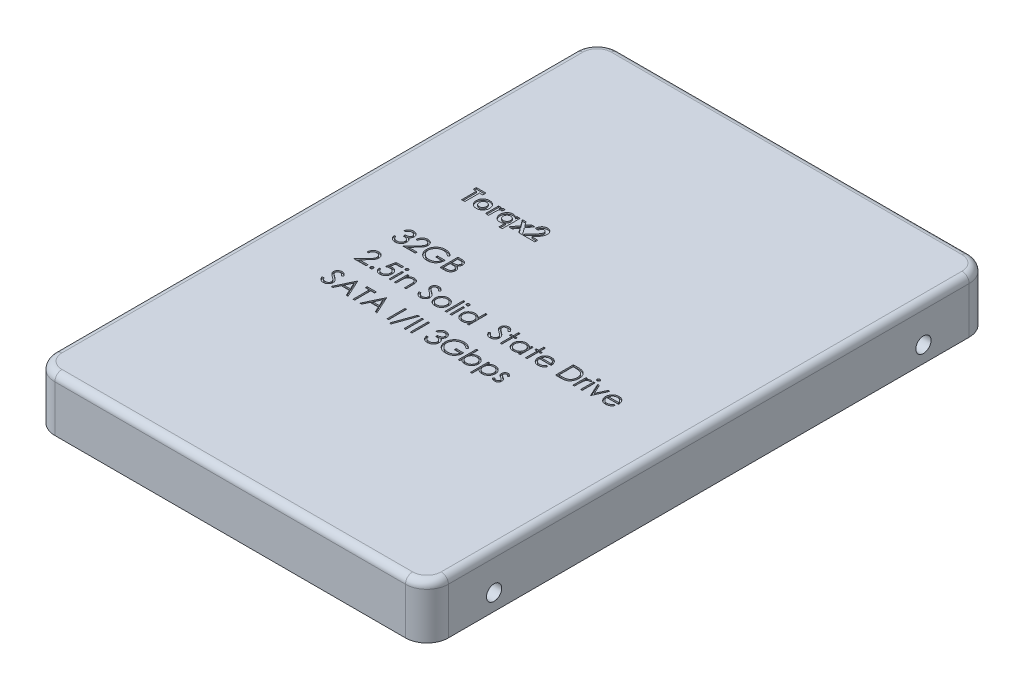
SolidWorks part; units mm, degrees
ref_plane "Front Plane" through (0, 0, 0) normal (0, 0, 1) x (1, 0, 0)
ref_plane "Top Plane" through (0, 0, 0) normal (0, 1, 0) x (1, 0, 0)
ref_plane "Right Plane" through (0, 0, 0) normal (1, 0, 0) x (0, 0, -1)
sketch "Sketch1" plane through (0, 0, 0) normal (0, 1, 0) x (1, 0, 0)
  line L1 (-34.925, -50.0253) -> (34.925, -50.0253)
  line L2 (-34.925, -50.0253) -> (-34.925, 50.0253)
  line L3 (-34.925, 50.0253) -> (34.925, 50.0253)
  line L4 (34.925, -50.0253) -> (34.925, 50.0253)
  line L5 (-34.925, -50.0253) -> (34.925, 50.0253) construction
  line L6 (-34.925, 50.0253) -> (34.925, -50.0253) construction
  point P0 (0, 0)
  dimension "D1" = 100.0506
  dimension "D2" = 69.85
extrude "Boss-Extrude1" add sketch "Sketch1" along normal mid plane 9.525
fillet "Fillet1" radius 3.81 4 edges at (-34.925, 0, -50.0253) (34.925, 0, -50.0253) (-34.925, 0, 50.0253) (34.925, 0, 50.0253)
fillet "Fillet2" radius 1.27 8 edges at (-33.8091, 4.7625, -48.9094) (0, 4.7625, -50.0253) (33.8091, 4.7625, -48.9094) (34.925, 4.7625, 0) (33.8091, 4.7625, 48.9094) (0, 4.7625, 50.0253) (-33.8091, 4.7625, 48.9094) (-34.925, 4.7625, 0)
hole_wizard "#6-32 Tapped Hole1" positions "Sketch3" profile "Sketch2" tap size "#6-32" standard "Ansi Inch"
sketch "Sketch3" plane through (0, -4.7625, 0) normal (0, -1, 0) x (1, 0, 0)
  line L1 (-30.7975, -38.1) -> (30.7975, -38.1) construction
  line L2 (-30.7975, -38.1) -> (-30.7975, 38.1) construction
  line L3 (-30.7975, 38.1) -> (30.7975, 38.1) construction
  line L4 (30.7975, -38.1) -> (30.7975, 38.1) construction
  line L5 (-30.7975, -38.1) -> (30.7975, 38.1) construction
  line L6 (-30.7975, 38.1) -> (30.7975, -38.1) construction
  point P0 (-30.7975, -38.1)
  point P212 (0, 0)
  point P214 (-30.7975, 38.1)
  point P216 (30.7975, 38.1)
  point P218 (30.7975, -38.1)
  dimension "D1" = 76.2
  dimension "D2" = 61.595
sketch "Sketch2" plane through (-30.7975, -4.7625, -38.1) normal (1, 0, 0) x (0, 0, -1)
  line L0 (0, 0) -> (0, 5.8927)
  line L1 (0, 5.8927) -> (1.3525, 5.08)
  line L2 (1.3525, 5.08) -> (1.3525, 0)
  line L5 (1.3525, 0) -> (0, 0)
  line L10 (0, 5.8927) -> (-1.3526, 5.08) construction
  line L11 (0, -6.35) -> (0, 107.95) construction
  dimension "Tap Drill Dia." = 2.7051
  dimension "Tap Drill Depth" = 5.08
  dimension "Drill Angle" = 118
hole_wizard "#6-32 Tapped Hole2" positions "Sketch5" profile "Sketch4" tap size "#6-32" standard "Ansi Inch"
sketch "Sketch5" plane through (-34.925, 0, 0) normal (-1, 0, 0) x (0, 0, 1)
  line L0 (-38.1, -1.8415) -> (38.1, -1.8415) construction
  line L2 (-46.2153, -4.7625) -> (46.2153, -4.7625) construction
  point P0 (38.1, -1.8415)
  point P6 (0, -1.8415)
  point P10 (-38.1, -1.8415)
  dimension "D1" = 2.921
  dimension "D2" = 76.2
sketch "Sketch4" plane through (-34.925, -1.8415, 38.1) normal (0, 1, 0) x (0, 0, 1)
  line L0 (0, 0) -> (0, 5.8927)
  line L1 (0, 5.8927) -> (1.3525, 5.08)
  line L2 (1.3525, 5.08) -> (1.3525, 0)
  line L5 (1.3525, 0) -> (0, 0)
  line L10 (0, 5.8927) -> (-1.3526, 5.08) construction
  line L11 (0, -6.35) -> (0, 107.95) construction
  dimension "Tap Drill Dia." = 2.7051
  dimension "Tap Drill Depth" = 5.08
  dimension "Drill Angle" = 118
mirror "Mirror1" about plane through (0, 0, 0) normal (1, 0, 0) of "#6-32 Tapped Hole2"
sketch "Sketch6" plane through (0, 4.7625, 0) normal (0, 1, 0) x (1, 0, 0)
  text T0 "<b>Torqx2</b>\r\n\r\n32GB\r\n2.5in Solid  State Drive\r\nSATA I/II 3Gbps\r\n"
extrude "Cut-Extrude1" cut sketch "Sketch6" against normal blind 0.254
